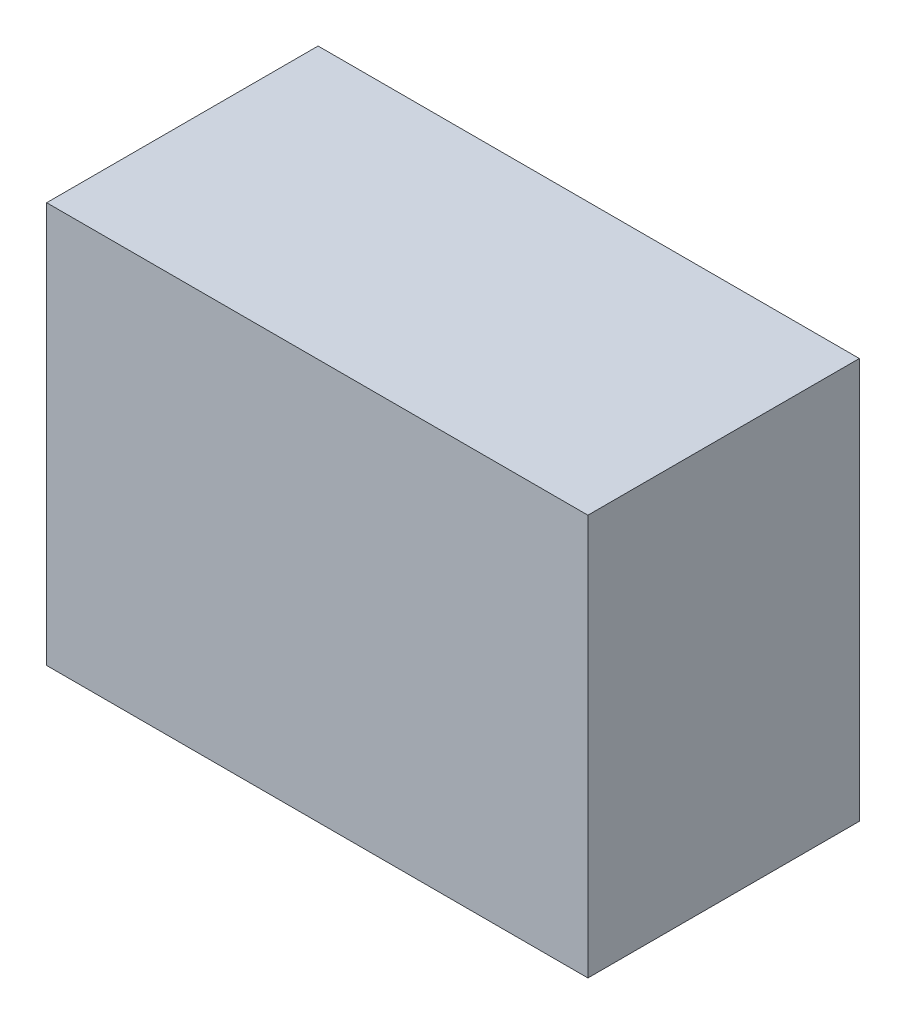
SolidWorks part; units mm, degrees
ref_plane "Front Plane" through (0, 0, 0) normal (0, 0, 1) x (1, 0, 0)
ref_plane "Top Plane" through (0, 0, 0) normal (0, 1, 0) x (1, 0, 0)
ref_plane "Right Plane" through (0, 0, 0) normal (1, 0, 0) x (0, 0, -1)
sketch "Sketch1" plane through (0, 0, 0) normal (0, 1, 0) x (1, 0, 0)
  line L1 (-171.5, -86) -> (171.5, -86)
  line L2 (-171.5, -86) -> (-171.5, 86)
  line L3 (-171.5, 86) -> (171.5, 86)
  line L4 (171.5, -86) -> (171.5, 86)
  line L5 (-171.5, -86) -> (171.5, 86) construction
  line L6 (-171.5, 86) -> (171.5, -86) construction
  point P0 (0, 0)
  dimension "D1" = 172
  dimension "D2" = 343
extrude "Boss-Extrude1" add sketch "Sketch1" along normal blind 254
